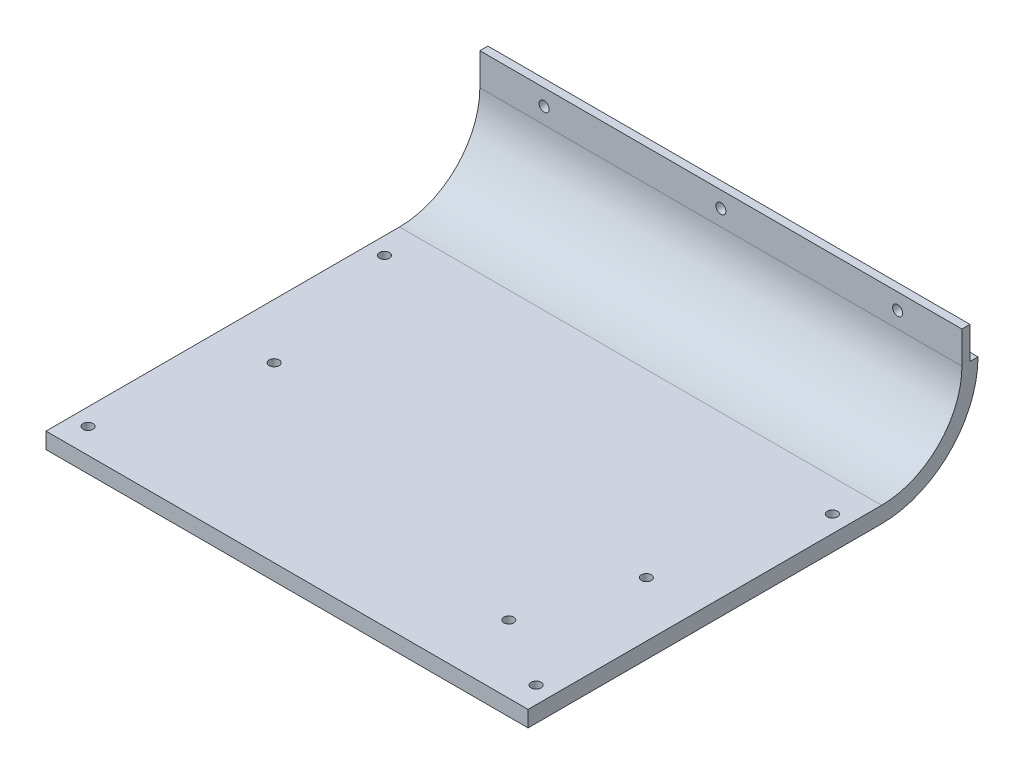
SolidWorks part; units mm, degrees
material "6061-T6 Aluminum"
ref_plane "Front Plane" through (0, 0, 0) normal (0, 0, 1) x (1, 0, 0)
ref_plane "Top Plane" through (0, 0, 0) normal (0, 1, 0) x (1, 0, 0)
ref_plane "Right Plane" through (0, 0, 0) normal (1, 0, 0) x (0, 0, -1)
sketch "Sketch1" plane through (0, 0, 0) normal (1, 0, 0) x (0, 0, -1)
  line L0 (-139.7, 0) -> (139.7, 0)
  line L5 (139.7, 0) -> (139.7, 12.7) construction
  line L7 (-139.7, 12.7) -> (139.7, 12.7)
  line L9 (-139.7, 0) -> (-139.7, 12.7)
  line L12 (139.7, 0) -> (139.7, 152.4) construction
  line L13 (0.6365, 139.0796) -> (-139.7417, 139.9778) construction
  line L14 (-12.6991, 151.8652) -> (-139.6605, 152.6775) construction
  line L15 (203.2, 76.2) -> (215.9, 76.2)
  arc A2 (139.7, 0) -> (-12.6991, 151.8652) centre (139.7, 152.4) ccw construction
  arc A3 (139.7, 12.7) -> (0.6365, 139.0796) centre (139.7, 152.4) ccw construction
  circle A5 centre (139.7, 76.2) radius 76.2 construction
  arc A6 (215.9, 76.2) -> (139.7, 0) centre (139.7, 76.2) cw
  circle A7 centre (139.7, 76.2) radius 63.5 construction
  arc A8 (203.2, 76.2) -> (139.7, 12.7) centre (139.7, 76.2) cw
  point P3 (0, 0)
  dimension "D1" = 152.4
  dimension "D2" = 12.7
  dimension "D4" = 127
  dimension "D6" = 12.7
  dimension "D3" = 12.7
  dimension "D5" = 12.7
  dimension "D7" = 355.6
extrude "Boss-Extrude1" add sketch "Sketch1" along normal blind 190.5 and the other way blind 190.5
sketch "Sketch2" plane through (0, 76.2, 0) normal (0, 1, 0) x (1, 0, 0)
  line L0 (-190.5, 215.9) -> (-190.5, 203.2) construction
  line L1 (-190.5, 209.55) -> (190.5, 209.55)
  line L2 (-190.5, 209.55) -> (-190.5, 203.2)
  line L3 (-190.5, 203.2) -> (190.5, 203.2)
  line L4 (190.5, 209.55) -> (190.5, 203.2)
extrude "Boss-Extrude2" add sketch "Sketch2" along normal blind 25.4
sketch "Sketch3" plane through (0, 0, -209.55) normal (0, 0, -1) x (-1, 0, 0)
  line L0 (-190.5, 88.9) -> (190.5, 88.9) construction
  line L1 (-190.5, 101.6) -> (-190.5, 76.2) construction
  line L2 (190.5, 101.6) -> (190.5, 76.2) construction
  line L3 (-139.7, 101.6) -> (-139.7, 76.2) construction
  line L4 (-190.5, 101.6) -> (190.5, 101.6) construction
  line L5 (-190.5, 76.2) -> (190.5, 76.2) construction
  line L6 (0, 101.6) -> (0, 76.2) construction
  line L7 (190.5, 76.2) -> (-190.5, 76.2) construction
  line L8 (139.7, 101.6) -> (139.7, 76.2) construction
  circle A0 centre (-139.7, 88.9) radius 3.9687
  circle A1 centre (139.7, 88.9) radius 3.9687
  circle A2 centre (0, 88.9) radius 3.9687
  dimension "D3" = 7.9375
  dimension "D1" = 139.7
  dimension "D2" = 139.7
extrude "Cut-Extrude1" cut sketch "Sketch3" against normal blind 25.4
sketch "Sketch4" plane through (0, 12.7, 0) normal (0, 1, 0) x (1, 0, 0)
  line L0 (0, -139.7) -> (0, -119.888) construction
  line L1 (-190.5, -139.7) -> (190.5, -139.7) construction
  line L2 (0, -119.888) -> (0, 0) construction
  line L3 (0, 0) -> (0, 114.3) construction
  line L4 (-147.066, -2.794) -> (147.066, -2.794) construction
  line L5 (-190.5, 139.7) -> (-190.5, -139.7) construction
  line L6 (-177.038, 114.3) -> (177.038, 114.3) construction
  line L7 (-121.666, -86.106) -> (121.666, -86.106) construction
  line L8 (-177.038, -119.888) -> (177.038, -119.888) construction
  line L10 (190.5, 139.7) -> (190.5, -139.7) construction
  circle A0 centre (177.038, -119.888) radius 3.937
  circle A2 centre (177.038, 114.3) radius 3.937
  circle A3 centre (-177.038, -119.888) radius 3.937
  circle A5 centre (-177.038, 114.3) radius 3.937
  circle A6 centre (147.066, -2.794) radius 3.937
  circle A7 centre (-147.066, -2.794) radius 3.937
  circle A8 centre (121.666, -86.106) radius 3.937
  point P12 (0, 114.3)
  point P15 (0, 0)
  point P19 (0, -119.888)
  dimension "D3" = 7.874
  dimension "D4" = 254
  dimension "D7" = 7.874
  dimension "D12" = 7.874
  dimension "D1" = 19.812
  dimension "D2" = 13.462
  dimension "D5" = 43.434
  dimension "D6" = 136.906
  dimension "D8" = 43.434
  dimension "D9" = 68.834
  dimension "D10" = 68.834
  dimension "D11" = 53.594
extrude "Cut-Extrude2" cut sketch "Sketch4" against normal through all
